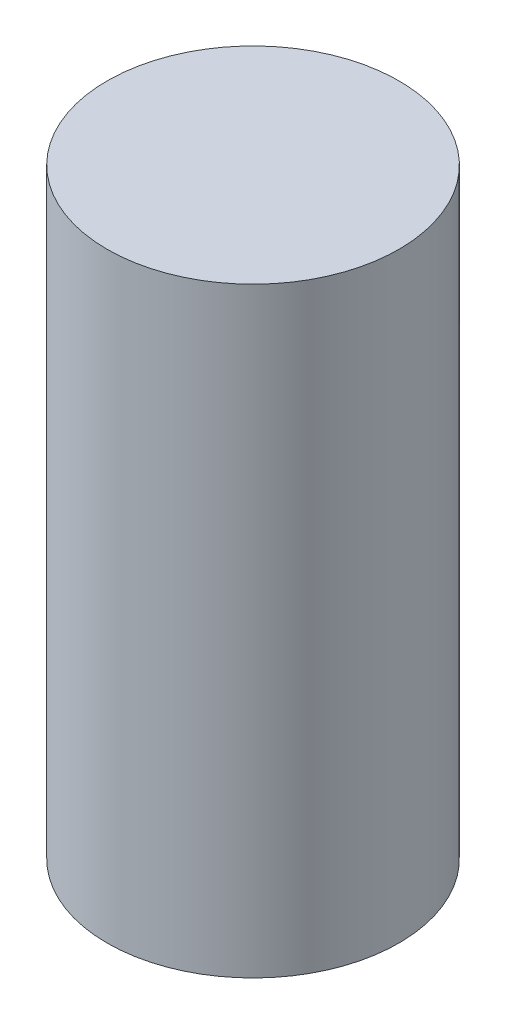
SolidWorks part; units mm, degrees
ref_plane "Front Plane" through (0, 0, 0) normal (0, 0, 1) x (1, 0, 0)
ref_plane "Top Plane" through (0, 0, 0) normal (0, 1, 0) x (1, 0, 0)
ref_plane "Right Plane" through (0, 0, 0) normal (1, 0, 0) x (0, 0, -1)
sketch "Sketch1" plane through (0, 0, 0) normal (0, 1, 0) x (1, 0, 0)
  circle A0 centre (0, 0) radius 34
  dimension "D1" = 68
extrude "Boss-Extrude1" add sketch "Sketch1" along normal blind 140
